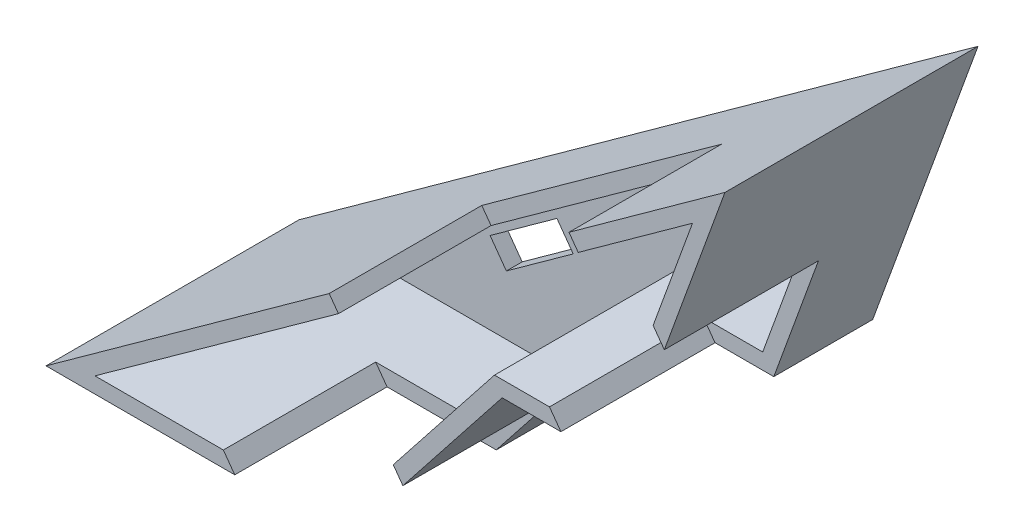
SolidWorks part; units mm, degrees
ref_plane "前视基准面" through (0, 0, 0) normal (0, 0, 1) x (1, 0, 0)
ref_plane "上视基准面" through (0, 0, 0) normal (0, 1, 0) x (1, 0, 0)
ref_plane "右视基准面" through (0, 0, 0) normal (1, 0, 0) x (0, 0, -1)
ref_plane "基准面4" through (0, 0, -30) normal (0, 0, 1) x (1, 0, 0)
sketch "草图2" plane through (0, 0, -30) normal (0, 0, 1) x (1, 0, 0)
  line L0 (134.559, 0.0916) -> (123.9494, -29.0581)
  line L1 (123.9494, -29.0581) -> (109.5193, -29.0581)
  line L2 (109.5193, -29.0581) -> (89.5141, -54.4009)
  line L3 (89.5141, -54.4009) -> (59.0008, -54.4009)
  line L4 (59.0008, -54.4009) -> (134.559, 0.0916)
  line L5 (90.4834, -56.4009) -> (110.7956, -30.6692) construction
  line L6 (125.4914, -30.6692) -> (138.6618, 5.5164) construction
  line L7 (138.6618, 5.5164) -> (52.8085, -56.4009) construction
  line L8 (52.8085, -56.4009) -> (90.4834, -56.4009) construction
  dimension "D1" = 2
  dimension "D2" = 2
  dimension "D3" = 2
  dimension "D4" = 2
ref_plane "基准面5" through (0, 0, 0) normal (0, 0, 1) x (1, 0, 0)
sketch "草图5" plane through (0, 0, 0) normal (0, 0, 1) x (1, 0, 0)
  line L14 (123.9494, -29.0581) -> (134.559, 0.0916)
  line L20 (109.5193, -29.0581) -> (123.9494, -29.0581)
  line L21 (89.5141, -54.4009) -> (109.5193, -29.0581)
  line L22 (59.0008, -54.4009) -> (89.5141, -54.4009)
  line L23 (134.559, 0.0916) -> (59.0008, -54.4009)
  line L24 (123.9494, -29.0581) -> (134.559, 0.0916)
  line L25 (109.5193, -29.0581) -> (123.9494, -29.0581)
  line L26 (89.5141, -54.4009) -> (109.5193, -29.0581)
  line L27 (59.0008, -54.4009) -> (89.5141, -54.4009)
  line L28 (134.559, 0.0916) -> (59.0008, -54.4009)
  dimension "D1" = 0
loft "放样2" add profiles "草图5", "草图2" connector at (123.9494, -29.0581, 0) connector at (123.9494, -29.0581, -30)
shell "抽壳3" thickness 2 removed face at (103.3085, -33.3653, 0) outward yes
sketch "草图10" plane through (45.9973, -63.779, 0) normal (0.5849, -0.8111, 0) x (0.8111, 0.5849, 0)
  line L0 (29.2007, 0) -> (29.2007, -19.2614)
  line L1 (59.11, 0) -> (-59.11, 0) construction
  line L2 (29.2007, -19.2614) -> (51.9661, -19.2614)
  line L3 (51.9661, -19.2614) -> (51.9661, 0)
  line L5 (71.4471, 0) -> (83.5006, 0) construction
  line L6 (77.4738, 0) -> (77.4738, -19.489)
  line L7 (77.4738, -19.489) -> (97.1555, -19.489)
  line L8 (97.1555, -19.489) -> (97.1555, 0)
  line L9 (83.5006, 0) -> (115.6917, 0) construction
  line M4 (109.1908, 0) -> (16.0324, 0)
  line M8 (109.1908, 0) -> (16.0324, 0)
extrude "切除-拉伸8" cut sketch "草图10" along normal blind 49 contours L2 L3 L0 M4 | L7 L8 L6 M8 region at (78.9135, -40.0399, -9.6307) region at (116.8159, -12.7048, -9.7445)
sketch "草图9" plane through (44.8274, -62.1569, 0) normal (-0.5849, 0.8111, 0) x (0.8111, 0.5849, 0)
  line L0 (53.9914, 0) -> (53.9914, 19.2971)
  line L1 (115.6917, 0) -> (9.8401, 0) construction
  line L2 (53.9914, 19.2971) -> (91.376, 19.2971)
  line L3 (91.376, 19.2971) -> (91.376, 0)
  line M7 (9.8401, 0) -> (115.6917, 0)
extrude "切除-拉伸5" cut sketch "草图9" against normal blind 10 contours L3 L2 L0 M7 region at (103.7792, -19.6409, -9.6486)
sketch "草图13" plane through (0, 0, -30) normal (0, 0, 1) x (1, 0, 0)
  line L0 (78.9639, -44.0483) -> (81.0234, -46.9039)
  line L1 (78.9639, -44.0483) -> (87.4171, -37.9519)
  line L2 (81.0234, -46.9039) -> (89.4765, -40.8075)
  line L3 (87.4171, -37.9519) -> (89.4765, -40.8075)
  line L4 (103.8801, -22.9555) -> (118.2257, -12.6095)
  line L5 (103.8801, -22.9555) -> (106.1257, -26.0692)
  line L6 (118.2257, -12.6095) -> (120.4713, -15.7232)
  line L7 (106.1257, -26.0692) -> (120.4713, -15.7232)
  line L9 (134.559, 0.0916) -> (59.0008, -54.4009) construction
extrude "切除-拉伸10" cut sketch "草图13" against normal blind 49
sketch "草图14" plane through (0, 0, -30) normal (0, 0, 1) x (1, 0, 0)
  circle A0 centre (70.8436, -49.5763) radius 1
  circle A1 centre (125.3974, -10.1234) radius 1
  point P0 (70.8436, -49.5763)
  point P2 (125.3974, -10.1234)
hole_wizard "#4-40 螺纹孔1" positions "草图14" profile "草图15" tap size "#4-40" standard "ANSI Inch" end condition through all
sketch "草图15" plane through (70.8436, -49.5763, -30) normal (1, 0, 0) x (0, -1, 0)
  line L0 (0, 0) -> (0, 2)
  line L1 (0, 2) -> (1.1303, 2)
  line L2 (1.1303, 2) -> (1.1303, 0)
  line L5 (1.1303, 0) -> (0, 0)
  line L11 (0, -6.35) -> (0, 107.95) construction
  dimension "通孔螺纹孔钻头直径" = 2.2606
  dimension "通孔螺纹孔钻头深度" = 2
cosmetic thread "孔螺纹线1" parameters "D2"=2.8448
cosmetic thread "孔螺纹线2" parameters "D2"=2.8448
sketch "草图22" plane through (0, 0, -32) normal (0, 0, -1) x (-1, 0, 0)
  point P0 (-116.6871, -21.5592)
hole_wizard "#4-40 螺纹孔2" positions "草图22" profile "草图21" tap size "#4-40" standard "ANSI Inch" end condition through all
sketch "草图21" plane through (116.6871, -21.5592, -32) normal (1, 0, 0) x (0, 1, 0)
  line L0 (0, 0) -> (0, 32.0001)
  line L1 (0, 32.0001) -> (1.1303, 32.0001)
  line L2 (1.1303, 32.0001) -> (1.1303, 0)
  line L5 (1.1303, 0) -> (0, 0)
  line L11 (0, -6.35) -> (0, 107.95) construction
  dimension "通孔螺纹孔钻头直径" = 2.2606
  dimension "通孔螺纹孔钻头深度" = 32.0001
cosmetic thread "孔螺纹线3"
